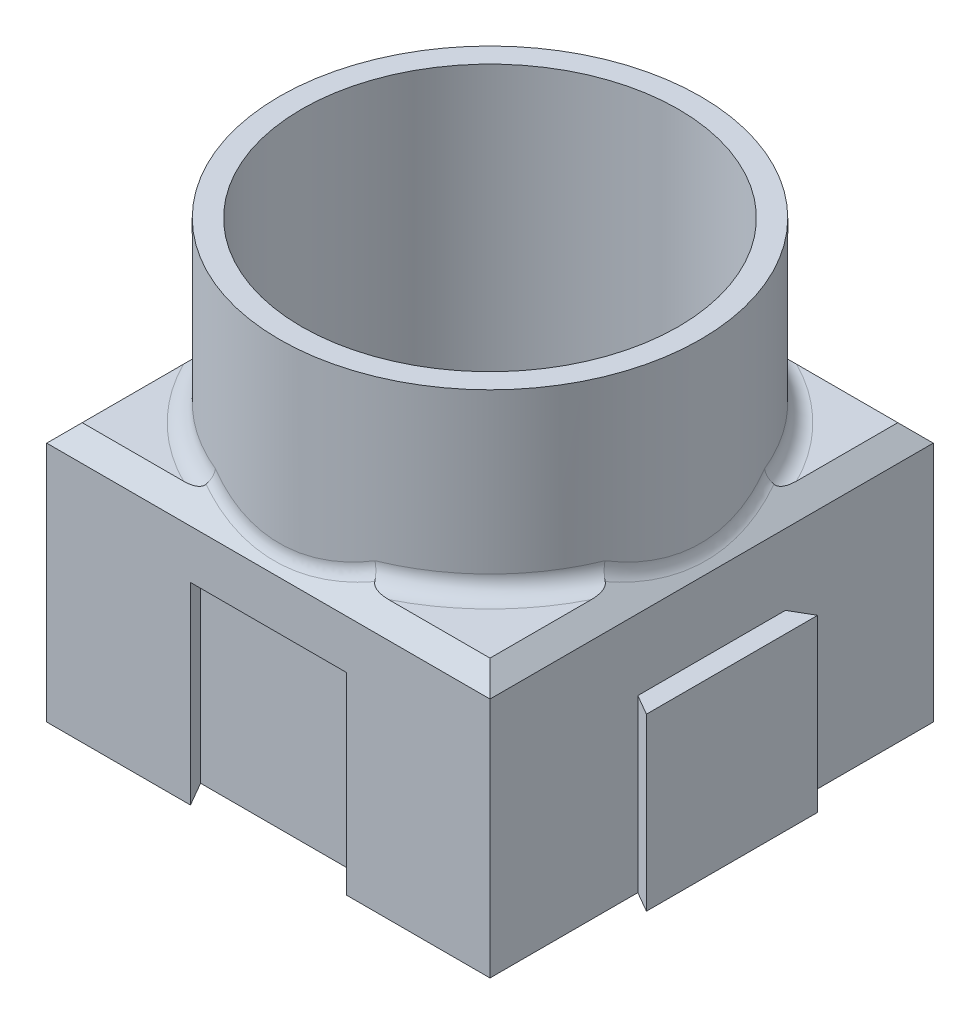
SolidWorks part; units mm, degrees
ref_plane "Left Plane" through (0, 0, 0) normal (0, 0, 1) x (1, 0, 0)
ref_plane "Bottom Plane" through (0, 0, 0) normal (0, 1, 0) x (1, 0, 0)
ref_plane "Back Plane" through (0, 0, 0) normal (1, 0, 0) x (0, 0, -1)
sketch "Sketch1" plane through (0, 0, 0) normal (0, 1, 0) x (1, 0, 0)
  line L1 (0, 0) -> (50, 0)
  line L2 (0, 0) -> (0, 50)
  line L3 (0, 50) -> (50, 50)
  line L4 (50, 0) -> (50, 50)
  dimension "D1" = 50
extrude "Boss-Extrude1" add sketch "Sketch1" along normal blind 30
sketch "Sketch2" plane through (0, 30, 0) normal (0, 1, 0) x (1, 0, 0)
  line L0 (0, 0) -> (50, 50) construction
  line L1 (0, 50) -> (50, 0) construction
  line L2 (25, 25) -> (3.75, 25) construction
  line L3 (3.75, 25) -> (1.25, 25) construction
  circle A0 centre (25, 25) radius 21.25
  circle A1 centre (25, 25) radius 23.75
  dimension "D1" = 42.5
  dimension "D2" = 2.5
extrude "Cut-Extrude1" cut sketch "Sketch2" against normal blind 26 contours A0
sketch "Sketch3" plane through (0, 0, 0) normal (0, 1, 0) x (1, 0, 0)
  line L0 (50, 33.5566) -> (52.5, 35) construction
  line L1 (50, 0) -> (50, 50) construction
  line L2 (52.5, 35) -> (52.5, 15) construction
  line L3 (52.5, 15) -> (50, 16.4434) construction
  line L4 (50, 25) -> (52.5, 25) construction
  line L5 (16.4434, 50) -> (15, 52.5) construction
  line L6 (50, 50) -> (0, 50) construction
  line L7 (15, 52.5) -> (35, 52.5) construction
  line L8 (35, 52.5) -> (33.5566, 50) construction
  line L9 (25, 52.5) -> (25, 50) construction
  line L10 (0, 33.5566) -> (2.5, 35) construction
  line L11 (0, 50) -> (0, 0) construction
  line L12 (2.5, 35) -> (2.5, 15) construction
  line L13 (2.5, 15) -> (0, 16.4434) construction
  line L14 (0, 25) -> (2.5, 25) construction
  line L15 (16.4434, 0) -> (15, 2.5) construction
  line L16 (0, 0) -> (50, 0) construction
  line L17 (15, 2.5) -> (35, 2.5) construction
  line L18 (35, 2.5) -> (33.5566, 0) construction
  line L19 (25, 0) -> (25, 2.5) construction
  line L20 (50, 16.6743) -> (50, 33.3257)
  line L21 (33.3257, 50) -> (16.6743, 50)
  line L23 (16.4434, 0) -> (33.5566, 0) construction
  line L24 (50, 33.3257) -> (52.3, 34.6536)
  line L25 (52.3, 34.6536) -> (52.3, 15.3464)
  line L26 (52.3, 15.3464) -> (50, 16.6743)
  line L27 (52.3, 34.6536) -> (52.2, 34.8268) construction
  line L28 (16.2124, 0) -> (14.6536, 2.7)
  line L29 (52.3, 34.6536) -> (52.5, 34.6536) construction
  line L30 (14.6536, 2.7) -> (35.3464, 2.7)
  line L31 (35.3464, 2.7) -> (33.7876, 0)
  line L32 (33.7876, 0) -> (16.2124, 0)
  line L33 (35, 2.5) -> (35, 2.7) construction
  line L34 (35, 2.5) -> (35.1732, 2.4) construction
  line L35 (0, 33.7876) -> (2.7, 35.3464)
  line L36 (2.7, 35.3464) -> (2.7, 14.6536)
  line L37 (2.7, 14.6536) -> (0, 16.2124)
  line L38 (0, 16.2124) -> (0, 33.7876)
  line L39 (2.4, 14.8268) -> (2.5, 15) construction
  line L40 (2.5, 15) -> (2.7, 15) construction
  line L41 (16.6743, 50) -> (15.3464, 52.3)
  line L42 (15.3464, 52.3) -> (34.6536, 52.3)
  line L43 (34.6536, 52.3) -> (33.3257, 50)
  line L44 (15.3464, 52.5) -> (15.3464, 52.3) construction
  line L45 (15.1732, 52.2) -> (15.3464, 52.3) construction
  point P8 (50, 25)
  point P39 (52.3, 25)
  point P40 (25, 0)
  point P53 (0, 25)
  point P59 (25, 52.3)
  point P63 (25, 50)
  dimension "D1" = 0.2
  dimension "D2" = 60
  dimension "D3" = 2.5
  dimension "D4" = 20
extrude "Boss-Extrude2" add sketch "Sketch3" along normal blind 20 contours L20 L24 L25 L26
extrude "Boss-Extrude3" add sketch "Sketch3<3>" along normal blind 20 contours L21 L41 L42 L43
sketch "Sketch3<3>" plane through (0, 0, 0) normal (0, 1, 0) x (1, 0, 0) same geometry as "Sketch3"
extrude "Cut-Extrude5" cut sketch "Sketch3<6>" along normal blind 20 contours L38 L35 L36 L37
sketch "Sketch3<6>" plane through (0, 0, 0) normal (0, 1, 0) x (1, 0, 0) same geometry as "Sketch3"
extrude "Cut-Extrude6" cut sketch "Sketch3<7>" along normal blind 20 contours L32 L28 L30 L31
sketch "Sketch3<7>" plane through (0, 0, 0) normal (0, 1, 0) x (1, 0, 0) same geometry as "Sketch3"
extrude "Boss-Extrude4" add sketch "Sketch2<3>" along normal blind 20
sketch "Sketch2<3>" plane through (0, 30, 0) normal (0, 1, 0) x (1, 0, 0) same geometry as "Sketch2"
chamfer "Chamfer1" distance 2 angle 45 4 edges at (25, 30, -50) (50, 30, -25) (25, 30, 0) (0, 30, -25)
sketch "Sketch4" plane through (0, 0, 0) normal (0, 1, 0) x (1, 0, 0)
  line L0 (12.5, 12.5) -> (37.5, 37.5) construction
  line L1 (12.5, 12.5) -> (37.5, 12.5) construction
  line L2 (12.5, 12.5) -> (12.5, 37.5) construction
  line L3 (12.5, 37.5) -> (37.5, 37.5) construction
  line L4 (37.5, 12.5) -> (37.5, 37.5) construction
  line L5 (12.5, 37.5) -> (37.5, 12.5) construction
  line L6 (0, 0) -> (12.5, 12.5) construction
  line L7 (12.5, 37.5) -> (0, 50) construction
  line L8 (50, 50) -> (37.5, 37.5) construction
  line L9 (50, 0) -> (37.5, 12.5) construction
  line L10 (0, 25) -> (25, 25) construction
  circle A0 centre (12.5, 37.5) radius 3.1
  circle A1 centre (37.5, 37.5) radius 3.1
  circle A2 centre (37.5, 12.5) radius 3.1
  circle A3 centre (12.5, 12.5) radius 3.1
  point P15 (12.5, 25)
  dimension "D1" = 6.2
extrude "Cut-Extrude4" cut sketch "Sketch4" along normal blind 4
chamfer "Chamfer3" distance 0.75 angle 45 24 edges at (41.8938, 0, 0) (50, 0, -8.3372) (50, 0, -41.6628) (41.6628, 0, -50) (8.3372, 0, -50) (0, 0, -41.8938) (0, 0, -8.1062) (8.1062, 0, 0) (12.5, 0, -34.4) (37.5, 0, -34.4) (37.5, 0, -9.4) (12.5, 0, -9.4) (51.15, 0, -16.0104) (52.3, 0, -25) (51.15, 0, -33.9896) (33.9896, 0, -51.15) (25, 0, -52.3) (16.0104, 0, -51.15) (1.35, 0, -34.567) (2.7, 0, -25) (1.35, 0, -15.433) (15.433, 0, -1.35) (25, 0, -2.7) (34.567, 0, -1.35)
chamfer "Chamfer4" distance 2.5 angle 45 2 edges at (25, 20, 0) (0, 20, -25)
fillet "Fillet1" radius 2 8 edges at (1.25, 29.25, -25) (8.2062, 30, -41.7938) (25, 29.25, -48.75) (41.7938, 30, -41.7938) (48.75, 29.25, -25) (41.7938, 30, -8.2062) (25, 29.25, -1.25) (8.2062, 30, -8.2062)
